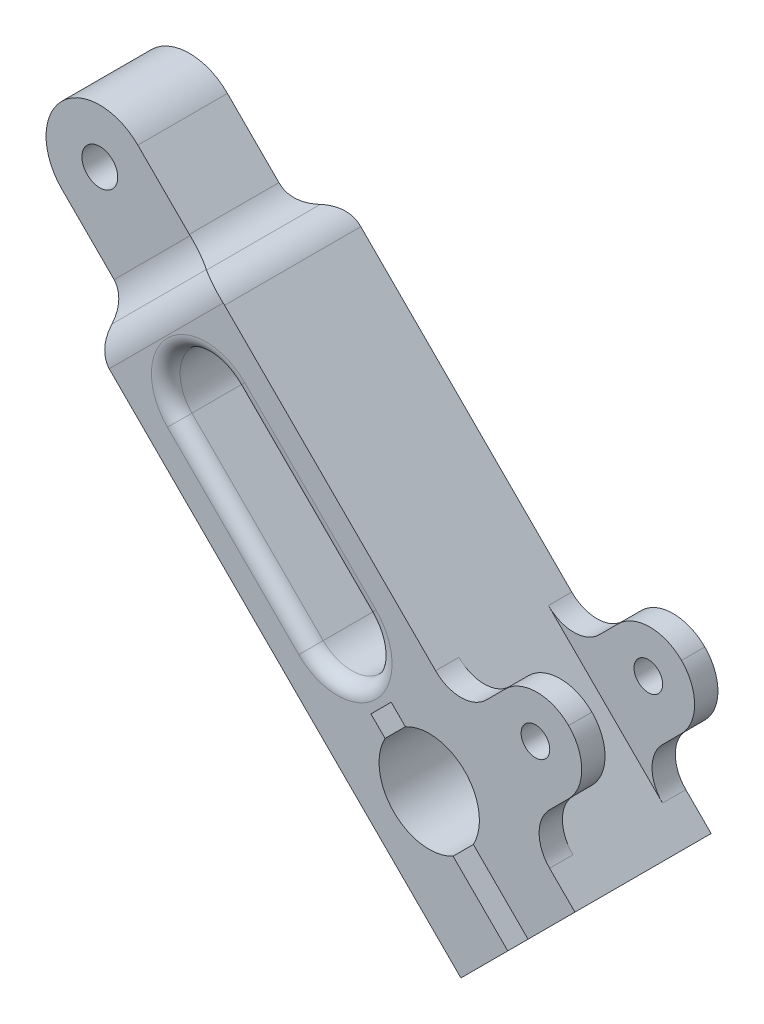
SolidWorks part; units mm, degrees
ref_plane "Front Plane" through (0, 0, 0) normal (0, 0, 1) x (1, 0, 0)
ref_plane "Top Plane" through (0, 0, 0) normal (0, 1, 0) x (1, 0, 0)
ref_plane "Right Plane" through (0, 0, 0) normal (1, 0, 0) x (0, 0, -1)
sketch "Sketch2" plane through (0, 0, 0) normal (0, 0, 1) x (1, 0, 0)
  line L0 (0, 0) -> (-234.0257, 0) construction
  line L1 (0, 0) -> (132.15, 132.15) construction
  line L2 (0, 0) -> (130.2279, -130.2279) construction
  line L3 (-10.6066, -10.6066) -> (10.6066, 10.6066) construction
  line L4 (-10.6066, -10.6066) -> (21.2132, -42.4264) construction
  line L5 (21.2132, -42.4264) -> (42.4264, -21.2132) construction
  line L6 (42.4264, -21.2132) -> (10.6066, 10.6066) construction
  line L7 (0, -21.2132) -> (21.2132, 0)
  line L9 (21.2132, 0) -> (53.033, -31.8198)
  line L10 (0, -21.2132) -> (31.8198, -53.033)
  line L11 (31.8198, -53.033) -> (26.5165, -58.3363)
  line L12 (114.318, -146.1378) -> (26.5165, -58.3363)
  line L13 (53.033, -31.8198) -> (58.3363, -26.5165)
  line L14 (128.4601, -96.6403) -> (58.3363, -26.5165)
  line L15 (146.1378, -114.318) -> (167.351, -93.1047)
  line L16 (167.351, -93.1047) -> (149.6733, -75.4271)
  line L17 (149.6733, -75.4271) -> (128.4601, -96.6403)
  line L18 (158.5121, -84.2659) -> (119.6213, -119.6213) construction
  line L19 (146.1378, -114.318) -> (160.2799, -128.4601)
  line L20 (114.318, -146.1378) -> (128.4601, -160.2799)
  line L21 (160.2799, -128.4601) -> (147.1984, -141.5416)
  line L22 (109.0147, -103.3578) -> (112.9628, -107.306)
  line L23 (103.3578, -109.0147) -> (109.0147, -103.3578)
  line L24 (103.3578, -109.0147) -> (107.306, -112.9628)
  line L25 (131.9365, -126.2797) -> (147.1984, -141.5416)
  line L26 (126.2797, -131.9365) -> (141.5416, -147.1984)
  line L27 (141.5416, -147.1984) -> (128.4601, -160.2799)
  line L28 (31.8198, -53.033) -> (53.033, -31.8198)
  line L29 (128.4601, -96.6403) -> (146.1378, -114.318)
  circle A0 centre (21.2132, -21.2132) radius 5
  circle A1 centre (149.2524, -92.6839) radius 4
  arc A2 (107.306, -112.9628) -> (126.2797, -131.9365) centre (119.6213, -119.6213) ccw
  arc A3 (131.9365, -126.2797) -> (112.9628, -107.306) centre (119.6213, -119.6213) ccw
  point P8 (0, 0)
  point P15 (10.6066, -10.6066)
  point P18 (130.2279, -130.2279)
  point P35 (111.5259, -126.9806)
  point P40 (106.1862, -106.1862)
  dimension "D4" = 10
  dimension "D5" = 15
  dimension "D12" = 8
  dimension "D13" = 12.5
  dimension "D14" = 28
  dimension "D1" = 184.17
  dimension "D2" = 30
  dimension "D3" = 45
  dimension "D6" = 15
  dimension "D7" = 30
  dimension "D8" = 45
  dimension "D9" = 45
  dimension "D10" = 30
  dimension "D11" = 25
  dimension "D15" = 20
  dimension "D17" = 19
extrude "Boss-Extrude1" add sketch "Sketch2" along normal blind 38 contours A3 L25 L21 L19 L29 L14 L13 L28 L11 L12 L20 L27 L26 A2 L24 L23 L22 region at (89.1363, -89.1363, 0)
extrude "Boss-Extrude2" add sketch "Sketch2<3>" along normal blind 6.5 contours L17 L29 L15 L16 A1 region at (139.4556, -86.4226, 0)
sketch "Sketch2<3>" plane through (0, 0, 0) normal (0, 0, 1) x (1, 0, 0) same geometry as "Sketch2"
fillet "Fillet1" radius 12.5 2 edges at (167.351, -93.1047, 3.25) (149.6733, -75.4271, 3.25)
ref_plane "Plane1" through (0, 0, 19) normal (0, 0, -1) x (-1, 0, 0)
mirror "Mirror1" about plane through (0, 0, 19) normal (0, 0, -1) of "Boss-Extrude2", "Fillet1"
sketch "Sketch3" plane through (42.4264, -42.4264, 0) normal (-0.7071, 0.7071, 0) x (0, 0, 1)
  line L0 (19, 71.4684) -> (19, -71.4684) construction
  line L1 (6.5, 15) -> (31.5, 15)
  line L2 (6.5, 15) -> (6.5, -15)
  line L3 (6.5, -15) -> (31.5, -15)
  line L4 (31.5, 15) -> (31.5, -15)
  line L5 (6.5, 15) -> (31.5, -15) construction
  line L6 (6.5, -15) -> (31.5, 15) construction
  point P0 (19, 0)
  dimension "D1" = 30
  dimension "D2" = 25
extrude "Boss-Extrude3" add sketch "Sketch3" along normal blind 45
sketch "Sketch4" plane through (0, 0, 31.5) normal (0, 0, 1) x (1, 0, 0)
  line L0 (10.6066, -10.6066) -> (31.8198, -31.8198) construction
  line L1 (0, -21.2132) -> (21.2132, 0) construction
  circle A0 centre (21.2132, -21.2132) radius 5
  dimension "D1" = 10
  dimension "D2" = 15
extrude "Cut-Extrude1" cut sketch "Sketch4" against normal through all
fillet "Fillet2" radius 15 2 edges at (21.2132, 0, 19) (0, -21.2132, 19)
sketch "Sketch5" plane through (144.37, -144.37, 0) normal (0.7071, -0.7071, 0) x (0, 0, -1)
  line L0 (-38, -13.25) -> (0, -13.25) construction
  line L1 (-38, -4) -> (-38, -22.5) construction
  line L2 (0, -4) -> (0, -22.5) construction
  circle A0 centre (-27, -13.25) radius 4
  circle A1 centre (-13, -13.25) radius 4
  dimension "D1" = 8
  dimension "D2" = 8
  dimension "D3" = 14
  dimension "D4" = 11
extrude "Cut-Extrude2" cut sketch "Sketch5" against normal blind 10
fillet "Fillet3" radius 10 8 edges at (42.4264, -42.4264, 31.5) (31.8198, -53.033, 19) (53.033, -31.8198, 19) (42.4264, -42.4264, 6.5) (128.4601, -96.6403, 34.75) (128.4601, -96.6403, 3.25) (146.1378, -114.318, 34.75) (146.1378, -114.318, 3.25)
fillet "Fillet4" radius 10 4 edges at (42.4264, -42.4264, 0) (26.5165, -58.3363, 19) (42.4264, -42.4264, 38) (58.3363, -26.5165, 19)
sketch "Sketch6" plane through (0, 0, 0) normal (0, 0, -1) x (-1, 0, 0)
  line L0 (-46.2369, -46.2369) -> (-106.1862, -106.1862) construction
  line L1 (-30.3374, -62.1364) -> (-62.1364, -30.3374) construction
  line L2 (-103.3578, -109.0147) -> (-109.0147, -103.3578) construction
  line L3 (-57.366, -57.366) -> (-93.9989, -93.9989) construction
  line L4 (-49.4111, -65.321) -> (-86.044, -101.9539)
  line L5 (-65.321, -49.4111) -> (-101.9539, -86.044)
  line L6 (-46.2369, -46.2369) -> (-7.1246, -7.4244) construction
  line L7 (-41.0197, -41.0197) -> (-31.4603, -31.5736) construction
  line L8 (-54.1799, -27.8596) -> (-27.8596, -54.1799) construction
  line L9 (-45.2948, -36.6935) -> (-35.7353, -27.2473)
  line L10 (-36.7447, -45.346) -> (-27.1853, -35.8999)
  arc A0 (-49.4111, -65.321) -> (-65.321, -49.4111) centre (-57.366, -57.366) ccw
  arc A1 (-101.9539, -86.044) -> (-86.044, -101.9539) centre (-93.9989, -93.9989) ccw
  arc A2 (-45.2948, -36.6935) -> (-36.7447, -45.346) centre (-41.0197, -41.0197) ccw
  arc A3 (-27.1853, -35.8999) -> (-35.7353, -27.2473) centre (-31.4603, -31.5736) ccw
  point P8 (-75.6825, -75.6825)
  point P18 (-36.24, -36.2967)
  dimension "D1" = 11.25
extrude "Cut-Extrude3" cut sketch "Sketch6" against normal through all contours L5 A1 L4 A0
fillet "Fillet5" radius 4 8 edges at (49.4111, -49.4111, 0) (83.6374, -67.7275, 0) (101.9539, -101.9539, 0) (101.9539, -101.9539, 38) (83.6374, -67.7275, 38) (49.4111, -49.4111, 38) (67.7275, -83.6374, 0) (67.7275, -83.6374, 38)
